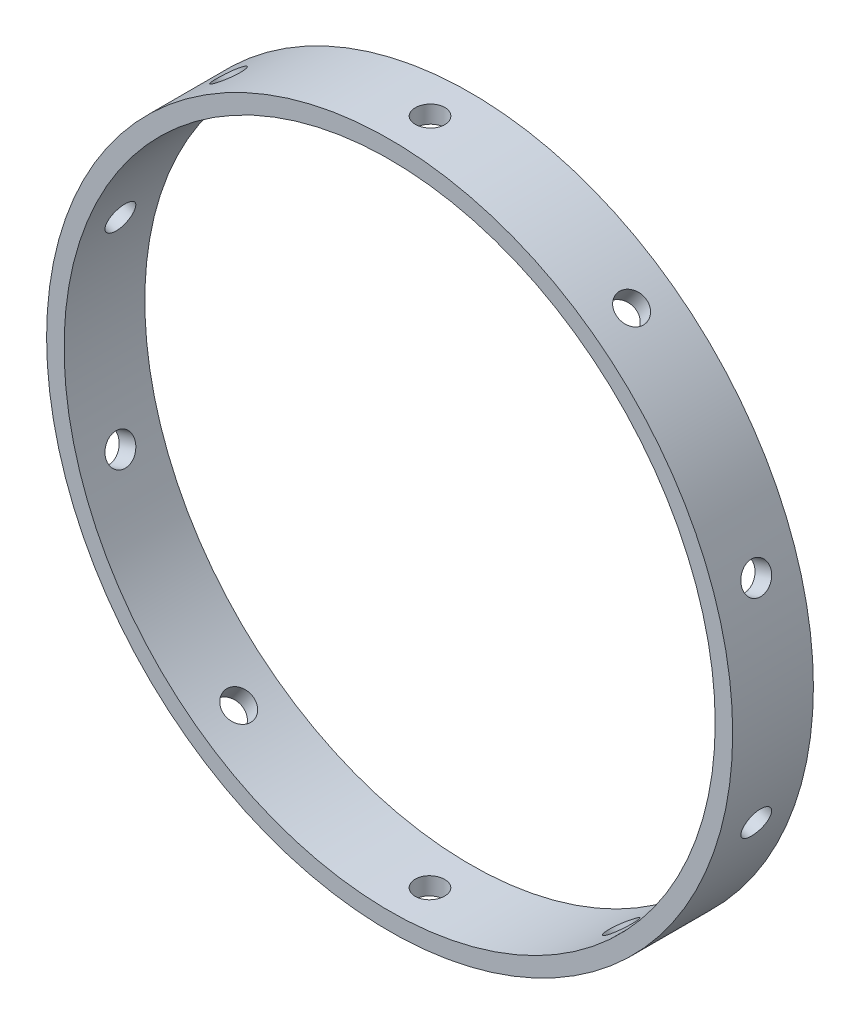
SolidWorks part; units mm, degrees
ref_plane "Front Plane" through (0, 0, 0) normal (0, 0, 1) x (1, 0, 0)
ref_plane "Top Plane" through (0, 0, 0) normal (0, 1, 0) x (1, 0, 0)
ref_plane "Right Plane" through (0, 0, 0) normal (1, 0, 0) x (0, 0, -1)
sketch "Sketch1" plane through (0, 0, 0) normal (0, 0, 1) x (1, 0, 0)
  circle A0 centre (0, 0) radius 76.835
  circle A1 centre (0, 0) radius 80.9625
  dimension "D1" = 153.67
  dimension "D2" = 161.925
extrude "Boss-Extrude1" add sketch "Sketch1" along normal blind 19.05
sketch "Sketch2" plane through (0, 0, 0) normal (0, 1, 0) x (1, 0, 0)
  line L0 (76.835, 0) -> (-76.835, 0) construction
  line L1 (0, -2.0807) -> (0, -15.8358) construction
  circle A0 centre (0, -9.525) radius 3.4782
  dimension "D1" = 9.525
extrude "Cut-Extrude1" cut sketch "Sketch2" against normal through all
ref_axis "Axis1" through (0, 0, 2.0807) along (0, 0, 1)
pattern_circular "CirPattern1" count 10 over 360 about axis through (0, 0, 2.0807) along (0, 0, 1) of "Cut-Extrude1"
